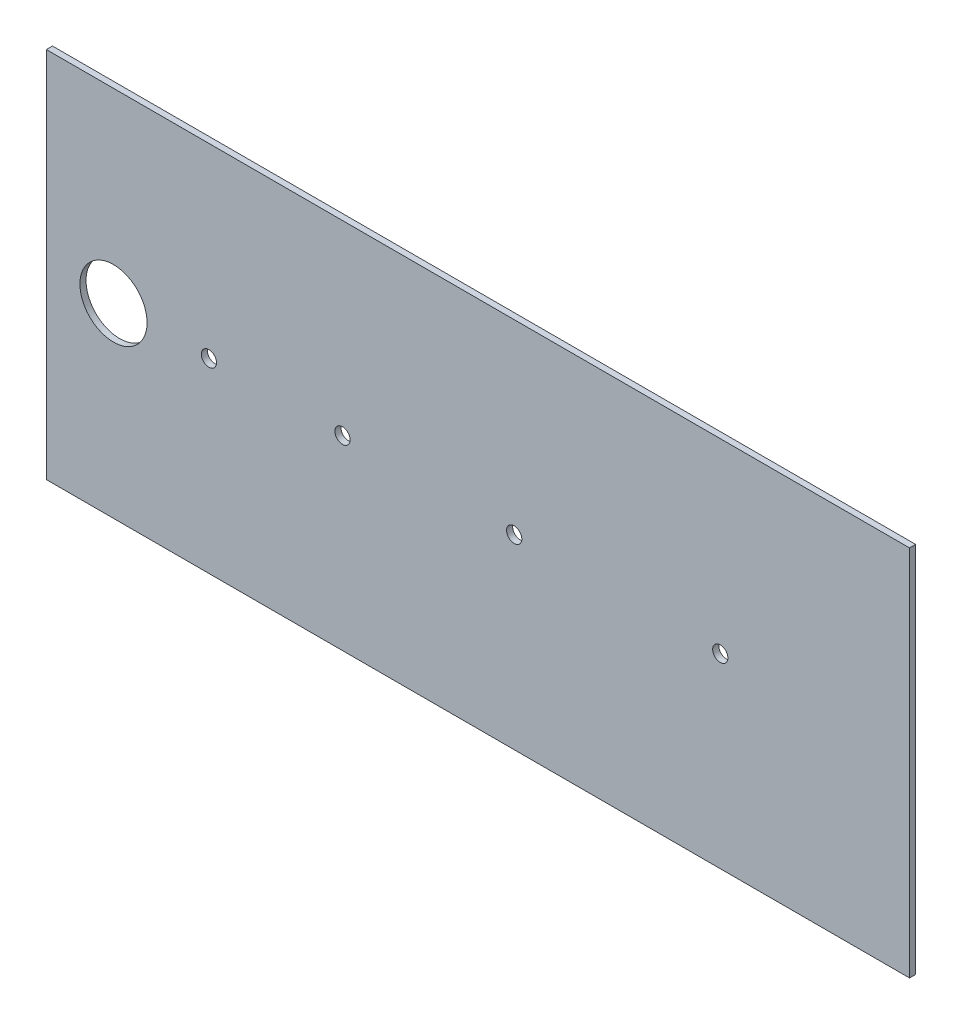
SolidWorks part; units mm, degrees
material "Сталь ШХ15 ГОСТ 801-78"
ref_plane "Plane1" through (0, 0, 0) normal (0, 0, 1) x (1, 0, 0)
ref_plane "Plane2" through (0, 0, 0) normal (0, 1, 0) x (1, 0, 0)
ref_plane "Plane3" through (0, 0, 0) normal (1, 0, 0) x (0, 0, -1)
sketch "Эскиз1" plane through (0, 0, 0) normal (0, 0, 1) x (1, 0, 0)
  line L0 (0, 61) -> (282.75, 61) construction
  line L1 (0, 0) -> (282.75, 0)
  line L2 (0, 0) -> (0, 122)
  line L3 (0, 122) -> (282.75, 122)
  line L4 (282.75, 0) -> (282.75, 122)
  circle A0 centre (22, 61) radius 11
  circle A1 centre (53.25, 61) radius 2.5
  circle A2 centre (97, 61) radius 2.5
  circle A3 centre (153.25, 61) radius 2.5
  circle A4 centre (220.75, 61) radius 2.5
  dimension "D3" = 22
  dimension "D4" = 22
  dimension "D5" = 5
  dimension "D6" = 31.25
  dimension "D9" = 62
  dimension "D1" = 122
  dimension "D2" = 67.5
  dimension "D7" = 43.75
  dimension "D8" = 56.25
extrude "Бобышка-Вытянуть1" add sketch "Эскиз1" along normal blind 2 contours L2 L0 A0 A1 A2 A3 A4 L4 L3 | L0 L2 L1 L4 A4 A3 A2 A1 A0 region at (142.732, 91.8564, 0) region at (142.732, 30.1436, 0)
